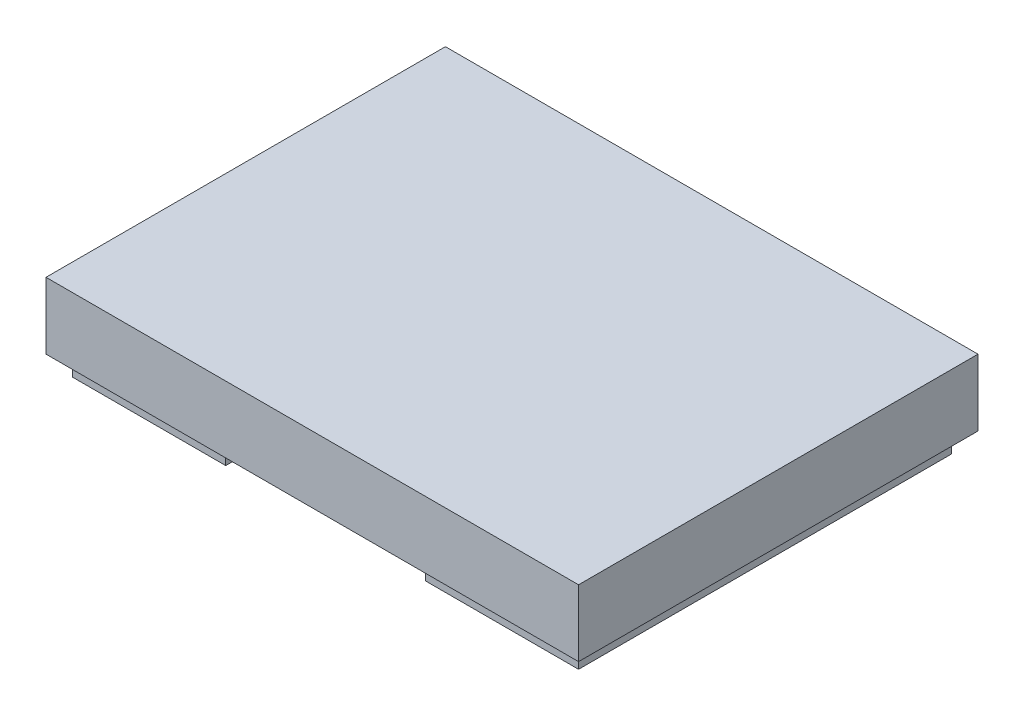
SolidWorks part; units mm, degrees
ref_plane "Front Plane" through (0, 0, 0) normal (0, 0, 1) x (1, 0, 0)
ref_plane "Top Plane" through (0, 0, 0) normal (0, 1, 0) x (1, 0, 0)
ref_plane "Right Plane" through (0, 0, 0) normal (1, 0, 0) x (0, 0, -1)
sketch "Sketch1" plane through (0, 0, 0) normal (0, 1, 0) x (1, 0, 0)
  line L1 (-50.8, 38.1) -> (50.8, 38.1)
  line L2 (-50.8, 38.1) -> (-50.8, -38.1)
  line L3 (-50.8, -38.1) -> (50.8, -38.1)
  line L4 (50.8, 38.1) -> (50.8, -38.1)
  line L5 (-50.8, 38.1) -> (50.8, -38.1) construction
  line L6 (-50.8, -38.1) -> (50.8, 38.1) construction
  point P0 (0, 0)
  dimension "D1" = 101.6
  dimension "D2" = 76.2
extrude "Boss-Extrude1" add sketch "Sketch1" along normal blind 12.7 separate body
sketch "Sketch2" plane through (0, 0, 0) normal (0, 1, 0) x (1, 0, 0)
  line L0 (-50.8, 38.1) -> (-50.8, -38.1) construction
  line L1 (-48.26, -35.56) -> (48.26, -35.56)
  line L2 (-48.26, -35.56) -> (-48.26, 35.56)
  line L3 (-48.26, 35.56) -> (48.26, 35.56)
  line L4 (48.26, -35.56) -> (48.26, 35.56)
  line L5 (-48.26, -35.56) -> (48.26, 35.56) construction
  line L6 (-48.26, 35.56) -> (48.26, -35.56) construction
  line L7 (-50.8, -38.1) -> (50.8, -38.1) construction
  point P0 (0, 0)
  dimension "D1" = 2.54
  dimension "D2" = 2.54
extrude "Boss-Extrude2" add sketch "Sketch2" against normal blind 3.81
shell "Shell1" thickness 2.54 removed face at (0, -3.81, 0)
sketch "Sketch3" plane through (0, 0, 0) normal (0, 1, 0) x (1, 0, 0)
  line L0 (-48.26, -35.56) -> (48.26, -35.56) construction
  line L1 (-19.05, -35.56) -> (19.05, -35.56)
  line L2 (-19.05, -35.56) -> (-19.05, -33.02)
  line L3 (-19.05, -33.02) -> (19.05, -33.02)
  line L4 (19.05, -35.56) -> (19.05, -33.02)
  line L5 (-45.72, -33.02) -> (45.72, -33.02) construction
  line L6 (0, 0) -> (0, -13.3167) construction
  dimension "D1" = 38.1
extrude "Cut-Extrude1" cut sketch "Sketch3" against normal blind 3.81
